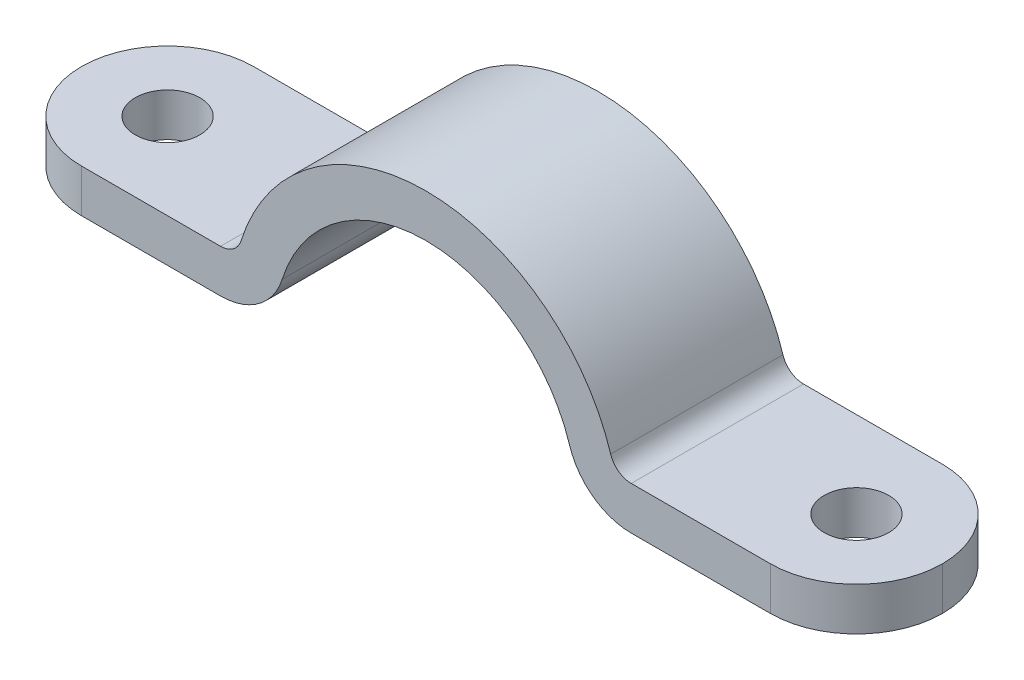
SolidWorks part; units mm, degrees
ref_plane "Front Plane" through (0, 0, 0) normal (0, 0, 1) x (1, 0, 0)
ref_plane "Top Plane" through (0, 0, 0) normal (0, 1, 0) x (1, 0, 0)
ref_plane "Right Plane" through (0, 0, 0) normal (1, 0, 0) x (0, 0, -1)
sketch "Sketch1" plane through (0, 0, 0) normal (0, 0, 1) x (1, 0, 0)
  line L0 (-100, 0) -> (-47.697, 0)
  line L1 (47.697, 0) -> (100, 0)
  line L2 (-100, 10) -> (-47.697, 10)
  line L3 (47.697, 10) -> (100, 10)
  line L4 (-100, 10) -> (-100, 0)
  line L5 (100, 10) -> (100, 0)
  arc A0 (33.3879, 10.5) -> (-33.3879, 10.5) centre (0, 0) ccw
  arc A1 (47.697, 0) -> (33.3879, 10.5) centre (47.697, 15) cw
  arc A2 (-33.3879, 10.5) -> (-47.697, 0) centre (-47.697, 15) cw
  arc A3 (-42.9273, 13.5) -> (-47.697, 10) centre (-47.697, 15) cw
  arc A4 (42.9273, 13.5) -> (-42.9273, 13.5) centre (0, 0) ccw
  arc A5 (47.697, 10) -> (42.9273, 13.5) centre (47.697, 15) cw
  point P8 (35, 0)
  dimension "D2" = 70
  dimension "D3" = 15
  dimension "D1" = 200
  dimension "D4" = 10
extrude "Boss-Extrude1" add sketch "Sketch1" along normal blind 40
fillet "Fillet1" radius 20 4 edges at (100, 5, 0) (100, 5, 40) (-100, 5, 0) (-100, 5, 40)
sketch "Sketch2" plane through (0, 10, 0) normal (0, 1, 0) x (1, 0, 0)
  circle A0 centre (-80, -20) radius 7.5
  circle A1 centre (80, -20) radius 7.5
  dimension "D1" = 15
extrude "Cut-Extrude1" cut sketch "Sketch2" against normal through all
